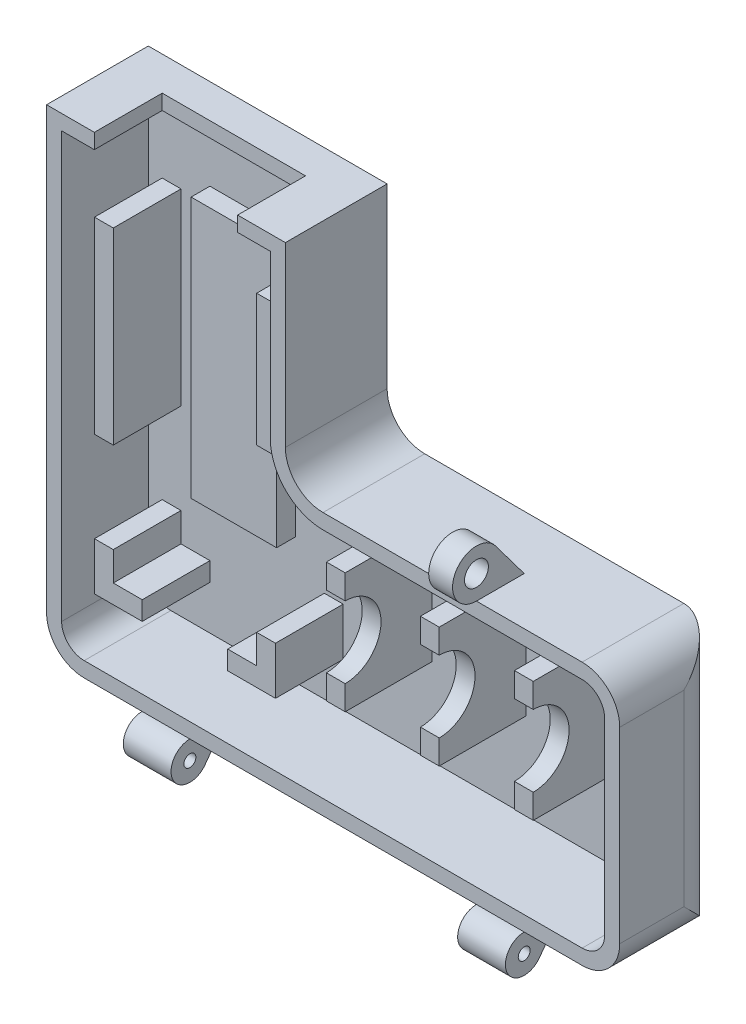
SolidWorks part; units mm, degrees
ref_plane "Alzado" through (0, 0, 0) normal (0, 0, 1) x (1, 0, 0)
ref_plane "Planta" through (0, 0, 0) normal (0, 1, 0) x (1, 0, 0)
ref_plane "Vista lateral" through (0, 0, 0) normal (1, 0, 0) x (0, 0, -1)
sketch "Croquis1" plane through (0, 0, 0) normal (0, 0, 1) x (1, 0, 0)
  line L0 (0, 0) -> (0, 127)
  line L1 (0, 127) -> (63.5, 127)
  line L2 (63.5, 69.85) -> (152.4, 69.85)
  line L3 (152.4, 0) -> (0, 0)
  line L4 (63.5, 69.85) -> (63.5, 127)
  line L5 (152.4, 69.85) -> (152.4, 0)
  dimension "D1" = 63.5
  dimension "D2" = 152.4
  dimension "D3" = 127
  dimension "D4" = 57.15
extrude "Saliente-Extruir1" add sketch "Croquis1" along normal blind 54.1
fillet "Redondeo1" radius 10 5 edges at (152.4, 34.925, 0) (0, 0, 27.05) (152.4, 0, 27.05) (152.4, 69.85, 27.05) (63.5, 69.85, 27.05)
sketch "Croquis2" plane through (152.4, 0, 0) normal (1, 0, 0) x (0, 0, -1)
  line L0 (0, 0) -> (-54.1, 0) construction
  line L1 (-54.1, 127) -> (-27.05, 127)
  line L2 (-54.1, 127) -> (-54.1, 0)
  line L3 (-54.1, 0) -> (-27.05, 0)
  line L4 (-27.05, 127) -> (-27.05, 0)
extrude "Cortar-Extruir1" cut sketch "Croquis2" against normal through all
shell "Vaciado1" thickness 4 removed face at (80.01, 54.9258, 27.05)
sketch "Croquis3" plane through (0, 0, 4) normal (0, 0, 1) x (1, 0, 0)
  line L0 (12.6847, 20.6881) -> (50.8153, 20.6881)
  line L1 (50.8153, 20.6881) -> (50.8153, 33.3881)
  line L2 (50.8153, 33.3881) -> (139.7153, 33.3881)
  line L3 (139.7153, 33.3881) -> (139.7153, 52.4381)
  line L4 (139.7153, 52.4381) -> (50.8153, 52.4381)
  line L5 (50.8153, 52.4381) -> (50.8153, 122.2881)
  line L6 (50.8153, 122.2881) -> (12.6847, 122.2881)
  line L7 (12.6847, 122.2881) -> (12.6847, 20.6881)
  line L8 (12.6847, 28.3881) -> (7.6847, 28.3881)
  line L9 (7.6847, 28.3881) -> (7.6847, 15.6881)
  line L10 (7.6847, 15.6881) -> (20.3847, 15.6881)
  line L11 (20.3847, 15.6881) -> (20.3847, 20.6881)
  line L12 (50.8153, 28.3881) -> (55.8153, 28.3881)
  line L13 (55.8153, 28.3881) -> (55.8153, 15.6881)
  line L14 (55.8153, 15.6881) -> (43.1153, 15.6881)
  line L15 (43.1153, 15.6881) -> (43.1153, 20.6881)
  line L16 (7.6847, 52.4381) -> (12.6847, 52.4381)
  line L17 (7.6847, 52.4381) -> (7.6847, 102.4381)
  line L18 (7.6847, 102.4381) -> (12.6847, 102.4381)
  line L19 (12.6847, 52.4381) -> (12.6847, 102.4381)
  line L20 (50.8153, 106.4881) -> (55.8153, 106.4881)
  line L21 (50.8153, 106.4881) -> (50.8153, 71.4881)
  line L22 (50.8153, 71.4881) -> (55.8153, 71.4881)
  line L23 (55.8153, 106.4881) -> (55.8153, 71.4881)
  line L24 (20.3847, 106.9132) -> (43.1153, 106.9132)
  line L25 (20.3847, 106.9132) -> (20.3847, 37.5203)
  line L26 (20.3847, 37.5203) -> (43.1153, 37.5203)
  line L27 (43.1153, 106.9132) -> (43.1153, 37.5203)
  line L28 (4, 123) -> (59.5, 123) construction
  point P30 (31.75, 122.2881)
  point P33 (31.75, 123)
  point P34 (31.75, 106.9132)
  dimension "D1" = 101.6
  dimension "D2" = 12.7
  dimension "D3" = 12.7
  dimension "D4" = 5
  dimension "D5" = 5
  dimension "D6" = 5
  dimension "D7" = 50
  dimension "D8" = 35
  dimension "D9" = 38.1306
extrude "Saliente-Extruir2" add sketch "Croquis3" along normal blind 5 contours L27 L24 L25 L26 region at (31.75, 72.2168, 4)
extrude "Saliente-Extruir3" add sketch "Croquis3<3>" along normal blind 18 contours L18 L17 L16 L7 | L23 L20 L5 L22 | L15 L14 L13 L12 L1 L0 | L10 L11 L0 L7 L8 L9 region at (12.5815, 20.5849, 4) region at (50.9185, 20.5849, 4) region at (10.1847, 77.4381, 4) region at (53.3153, 88.9881, 4)
sketch "Croquis3<3>" plane through (0, 0, 4) normal (0, 0, 1) x (1, 0, 0) same geometry as "Croquis3"
sketch "Croquis4" plane through (0, 0, 4) normal (0, 0, 1) x (1, 0, 0)
  line L0 (139.7153, 33.3881) -> (139.7153, 52.4381) construction
  line L1 (74.4, 58.9132) -> (79.4, 58.9132)
  line L2 (74.4, 58.9132) -> (74.4, 26.9131)
  line L3 (74.4, 26.9131) -> (79.4, 26.9131)
  line L4 (79.4, 58.9132) -> (79.4, 26.9131)
  line L5 (99.4, 58.9132) -> (104.4, 58.9132)
  line L6 (99.4, 58.9132) -> (99.4, 26.9131)
  line L7 (99.4, 26.9131) -> (104.4, 26.9131)
  line L8 (104.4, 58.9132) -> (104.4, 26.9131)
  line L9 (124.4, 58.9132) -> (129.4, 58.9132)
  line L10 (124.4, 58.9132) -> (124.4, 26.9131)
  line L11 (124.4, 26.9131) -> (129.4, 26.9131)
  line L12 (129.4, 58.9132) -> (129.4, 26.9131)
  line L13 (152.4, 10) -> (152.4, 59.85) construction
  point P12 (129.4, 42.9131)
  point P15 (139.7153, 42.9131)
  point P16 (104.4, 42.9131)
  point P17 (79.4, 42.9131)
  dimension "D1" = 5
  dimension "D2" = 23
  dimension "D3" = 20
  dimension "D4" = 20
  dimension "D5" = 32.0001
extrude "Saliente-Extruir4" add sketch "Croquis4" along normal up to surface (23.05 mm away) up to face at (80.01, 54.9258, 27.05)
sketch "Croquis5" plane through (129.4, 0, 0) normal (1, 0, 0) x (0, 0, -1)
  line L0 (-27.05, 58.9132) -> (-27.05, 26.9131) construction
  circle A0 centre (-27.05, 42.9131) radius 9.525
  dimension "D1" = 19.05
extrude "Cortar-Extruir2" cut sketch "Croquis5" against normal up to surface (73.5847 mm away) up to face at (55.8153, 22.0381, 13)
sketch "Croquis6" plane through (0, 123, 0) normal (0, -1, 0) x (1, 0, 0)
  line L0 (59.5, 4) -> (4, 4) construction
  line L1 (12.7, 9) -> (50.8, 9)
  line L2 (12.7, 9) -> (12.7, 51.2778)
  line L3 (12.7, 51.2778) -> (50.8, 51.2778)
  line L4 (50.8, 9) -> (50.8, 51.2778)
  point P6 (31.75, 4)
  point P7 (31.75, 9)
  dimension "D1" = 5
  dimension "D2" = 38.1
extrude "Cortar-Extruir3" cut sketch "Croquis6" against normal blind 18
ref_plane "Plano1" through (127, 0, 0) normal (1, 0, 0) x (0, 0, -1)
sketch "Croquis7" plane through (127, 0, 0) normal (1, 0, 0) x (0, 0, -1)
  line L0 (0, 0) -> (-27.05, 0) construction
  line L1 (-27.05, 0) -> (-17.144, 0)
  line L2 (-17.144, 0) -> (-23.0274, -7.9696)
  arc A0 (-27.05, 0) -> (-23.0274, -7.9696) centre (-27.05, -5) ccw
  dimension "D1" = 10
  dimension "D2" = 9.906
extrude "Saliente-Extruir5" add sketch "Croquis7" against normal blind 12.7
ref_plane "Plano2" through (25.4, 0, 0) normal (-1, 0, 0) x (0, 0, 1)
sketch "Croquis8" plane through (25.4, 0, 0) normal (-1, 0, 0) x (0, 0, 1)
  line L0 (23.0274, -7.9696) -> (17.144, 0)
  line L1 (17.144, 0) -> (27.05, 0)
  arc A0 (23.0274, -7.9696) -> (27.05, 0) centre (27.05, -5) ccw
extrude "Saliente-Extruir6" add sketch "Croquis8" against normal blind 12.7
sketch "Croquis9" plane through (127, 0, 0) normal (1, 0, 0) x (0, 0, -1)
  circle A0 centre (-27.05, -5) radius 1.5875
  dimension "D1" = 3.175
extrude "Cortar-Extruir4" cut sketch "Croquis9" against normal through all
ref_plane "Plano3" through (107.95, 0, 0) normal (1, 0, 0) x (0, 0, -1)
sketch "Croquis10" plane through (107.95, 0, 0) normal (1, 0, 0) x (0, 0, -1)
  line L0 (-27.05, 79.85) -> (-27.05, 69.85) construction
  line L2 (-21.97, 80.01) -> (-14.35, 69.85)
  line L3 (-14.35, 69.85) -> (-27.05, 69.85)
  line L6 (-27.05, 69.85) -> (0, 69.85) construction
  arc A0 (-21.97, 80.01) -> (-27.05, 69.85) centre (-27.05, 76.2) ccw
  circle A1 centre (-27.05, 76.2) radius 3.175
  point P1 (0, 0)
  point P11 (-27.05, 79.85)
  dimension "D1" = 12.7
  dimension "D2" = 6.35
  dimension "D3" = 12.7
extrude "Saliente-Extruir7" add sketch "Croquis10" along normal blind 6.35
